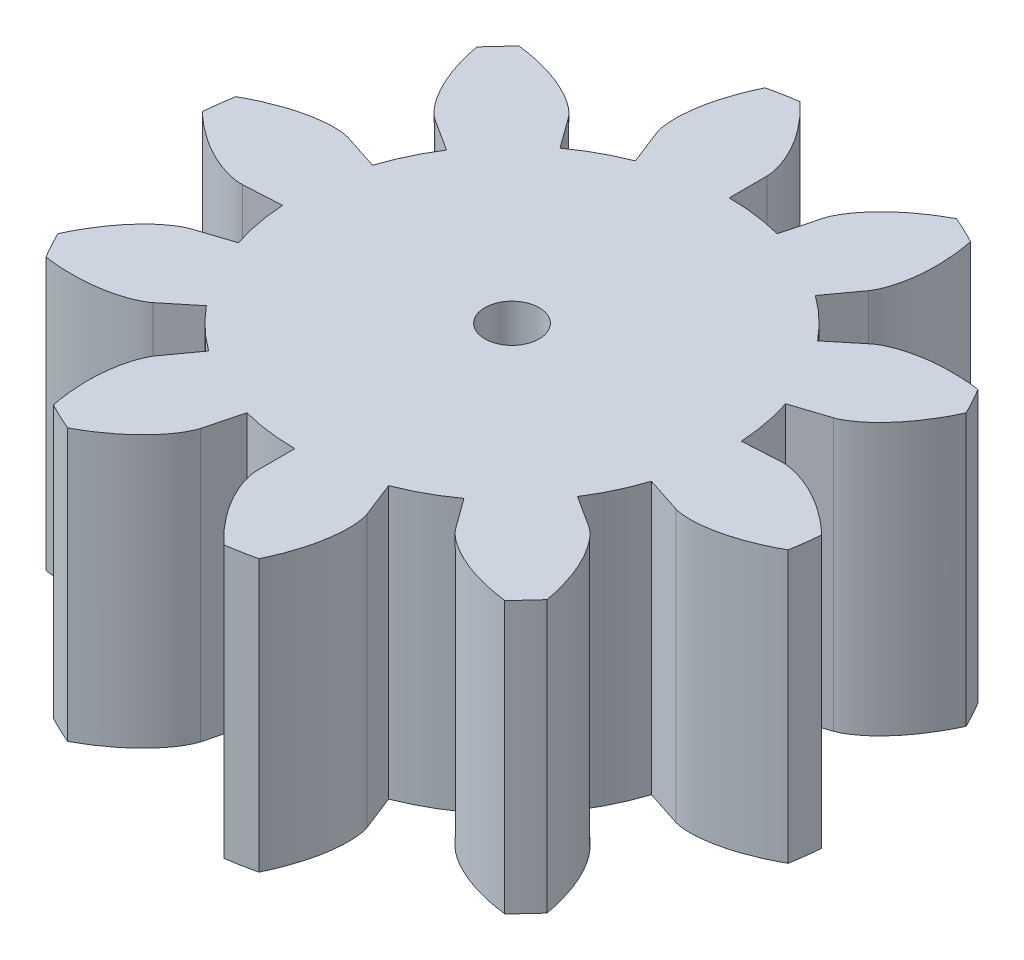
SolidWorks part; units mm, degrees
ref_plane "Front Plane" through (0, 0, 0) normal (0, 0, 1) x (1, 0, 0)
ref_plane "Top Plane" through (0, 0, 0) normal (0, 1, 0) x (1, 0, 0)
ref_plane "Right Plane" through (0, 0, 0) normal (1, 0, 0) x (0, 0, -1)
sketch "Reference attributes" plane through (0, 0, 0) normal (0, 1, 0) x (1, 0, 0)
  line L0 (0, 0) -> (10, 0) construction
  line L1 (0, -10) -> (2, -10) construction
  line L2 (0, 0) -> (9.6593, 2.5882) construction
  line L3 (0, 0) -> (9.3969, 3.4202) construction
  dimension "Teeth" = 10
  dimension "Module" = 2
  dimension "D2" = 10
  dimension "Helix Angle" = 15
  dimension "Pressure angle" = 20
sketch "Gear billet" plane through (0, 0, 0) normal (0, 1, 0) x (1, 0, 0)
  circle A0 centre (0, 0) radius 12.5
  dimension "OuterDi" = 25
extrude "Gear billet Extrude" add sketch "Gear billet" along normal blind 10
ref_plane "Opposite gear face" through (0, 10, 0) normal (0, 1, 0) x (1, 0, 0)
ref_point "Twist centre point top"
ref_point "Twist centre point bottom"
ref_axis "Axis" through (0, 10, 0) along (0, -1, 0)
sketch "Involute Profile" plane through (0, 10, 0) normal (0, 1, 0) x (1, 0, 0)
  line L0 (0, 0) -> (0, 9.3969) construction
  line L1 (0, 0) -> (2.3827, 9.0898) construction
  circle A0 centre (0, 0) radius 10.5
  circle A4 centre (0, 0) radius 9.3969 construction
  spline S0 degree 4 poles (0, 9.3969) (0, 9.4259) (-0.0038, 9.5071) (-0.0266, 9.6606) (-0.0851, 9.9058) (-0.1922, 10.2147) (-0.3651, 10.5975) (-0.6097, 11.0246) (-0.9202, 11.4673) (-1.2957, 11.9131) (-1.705, 12.3279) (-2.1431, 12.7121) (-2.6286, 13.0837) (-3.259, 13.5029) (-4.0497, 13.94) (-5.0111, 14.3602) (-6.121, 14.7192) (-7.2579, 14.9752) (-8.4139, 15.1318) (-9.5763, 15.1949) (-10.744, 15.1661) (-11.8996, 15.0541) (-13.0558, 14.8555) (-14.0345, 14.6214) (-14.8913, 14.3621) (-15.4972, 14.1535) (-16.03, 13.95) (-16.3797, 13.8071) (-16.869, 13.5964) (-17.2328, 13.4235) (-17.5961, 13.248) (-17.7759, 13.1522) (-17.8926, 13.0925) knots 0 0 0 0 0 0.005604 0.015718 0.02996 0.048734 0.068727 0.096889 0.125051 0.153212 0.181374 0.209535 0.237696 0.271429 0.327752 0.384075 0.440398 0.496721 0.553044 0.609367 0.66569 0.722013 0.778336 0.834659 0.86282 0.890982 0.909091 0.931818 0.954545 0.977273 1 1 1 1 1 construction
  spline S1 degree 4 poles (0, 9.3969) (0, 9.4259) (-0.0038, 9.5071) (-0.0266, 9.6606) (-0.0851, 9.9058) (-0.1922, 10.2147) (-0.3651, 10.5975) (-0.6097, 11.0246) (-0.9202, 11.4673) (-1.2957, 11.9131) (-1.705, 12.3279) (-2.1431, 12.7121) (-2.6286, 13.0837) (-3.259, 13.5029) (-4.0497, 13.94) (-5.0111, 14.3602) (-6.121, 14.7192) (-7.2579, 14.9752) (-8.4139, 15.1318) (-9.5763, 15.1949) (-10.744, 15.1661) (-11.8996, 15.0541) (-13.0558, 14.8555) (-14.0345, 14.6214) (-14.8913, 14.3621) (-15.4972, 14.1535) (-15.9054, 13.9976) (-16.1073, 13.9173) (-16.1861, 13.8853) knots 0 0 0 0 0 0.005604 0.015718 0.02996 0.048734 0.068727 0.096889 0.125051 0.153212 0.181374 0.209535 0.237696 0.271429 0.327752 0.384075 0.440398 0.496721 0.553044 0.609367 0.66569 0.722013 0.778336 0.834659 0.86282 0.890982 0.909091 0.909091 0.909091 0.909091 0.909091
  spline S2 degree 4 poles (2.3827, 9.0898) (2.3901, 9.1179) (2.4144, 9.1954) (2.4753, 9.3382) (2.5941, 9.5605) (2.776, 9.8321) (3.0403, 10.1585) (3.3853, 10.5097) (3.7979, 10.8592) (4.2741, 11.1952) (4.7752, 11.4927) (5.2964, 11.7532) (5.8603, 11.9896) (6.5764, 12.2353) (7.452, 12.4575) (8.4886, 12.6202) (9.6532, 12.6861) (10.8179, 12.6455) (11.9759, 12.5038) (13.1163, 12.27) (14.2385, 11.9461) (15.3279, 11.5447) (16.3959, 11.0595) (17.2833, 10.5849) (18.0464, 10.1168) (18.5796, 9.7614) (19.0434, 9.4294) (19.3453, 9.2025) (19.7652, 8.8746) (20.0733, 8.6152) (20.3803, 8.3532) (20.5299, 8.215) (20.6277, 8.1276) knots 0 0 0 0 0 0.005604 0.015718 0.02996 0.048734 0.068727 0.096889 0.125051 0.153212 0.181374 0.209535 0.237696 0.271429 0.327752 0.384075 0.440398 0.496721 0.553044 0.609367 0.66569 0.722013 0.778336 0.834659 0.86282 0.890982 0.909091 0.931818 0.954545 0.977273 1 1 1 1 1 construction
  spline S3 degree 4 poles (2.3827, 9.0898) (2.3901, 9.1179) (2.4144, 9.1954) (2.4753, 9.3382) (2.5941, 9.5605) (2.776, 9.8321) (3.0403, 10.1585) (3.3853, 10.5097) (3.7979, 10.8592) (4.2741, 11.1952) (4.7752, 11.4927) (5.2964, 11.7532) (5.8603, 11.9896) (6.5764, 12.2353) (7.452, 12.4575) (8.4886, 12.6202) (9.6532, 12.6861) (10.8179, 12.6455) (11.9759, 12.5038) (13.1163, 12.27) (14.2385, 11.9461) (15.3279, 11.5447) (16.3959, 11.0595) (17.2833, 10.5849) (18.0464, 10.1168) (18.5796, 9.7614) (18.9349, 9.5071) (19.1098, 9.3782) (19.1779, 9.3273) knots 0 0 0 0 0 0.005604 0.015718 0.02996 0.048734 0.068727 0.096889 0.125051 0.153212 0.181374 0.209535 0.237696 0.271429 0.327752 0.384075 0.440398 0.496721 0.553044 0.609367 0.66569 0.722013 0.778336 0.834659 0.86282 0.890982 0.909091 0.909091 0.909091 0.909091 0.909091
  point P6 (-0.324, 10.495)
  point P11 (2.9746, 10.0698)
  dimension "BaseDi" = 18.7939
  dimension "Adjusted Reference Diameter" = 21
  dimension "Reference Circumferential pitch" = 3.2987
sketch "Tooth profile" plane through (0, 10, 0) normal (0, 1, 0) x (1, 0, 0)
  line L0 (0, 0) -> (0, 9.3969) construction
  line L1 (0, 0) -> (2.3827, 9.0898) construction
  line L2 (0, 0) -> (0, 9.3969)
  line L3 (0, 0) -> (2.3827, 9.0898)
  line L4 (-0.2, -1.5517) -> (-0.2, 9.3969) construction
  line L5 (-0.2, -1.5517) -> (2.5762, 9.0391) construction
  circle A0 centre (0, 0) radius 12.5 construction
  circle A1 centre (0, 0) radius 12.5
  circle A2 centre (0, 0) radius 8
  spline S0 degree 1 poles (-0.2, 9.3969) (-16.1108, 13.7) knots 0 0 1 1 construction
  spline S1 degree 4 poles (-1998.2492, 88.8187) (-50.4033, 5.2802) (-1.0936, 5.8123) (0.3671, 8.0116) (-0.0851, 9.9058) (-0.1922, 10.2147) (-0.3651, 10.5975) (-0.6097, 11.0246) (-0.9202, 11.4673) (-1.2957, 11.9131) (-1.705, 12.3279) (-2.1431, 12.7121) (-2.6286, 13.0837) (-3.259, 13.5029) (-4.0497, 13.94) (-5.0111, 14.3602) (-6.121, 14.7192) (-7.2579, 14.9752) (-8.4139, 15.1318) (-9.5763, 15.1949) (-10.744, 15.1661) (-11.8996, 15.0541) (-13.0558, 14.8555) (-14.0345, 14.6214) (-14.8913, 14.3621) (-17.0967, 13.603) (-21.053, 11.7501) (19.7443, 27.8049) (-1868.6592, -739.8621) knots -0.32772 -0.32772 -0.32772 -0.32772 -0.32772 0.005604 0.015718 0.02996 0.048734 0.068727 0.096889 0.125051 0.153212 0.181374 0.209535 0.237696 0.271429 0.327752 0.384075 0.440398 0.496721 0.553044 0.609367 0.66569 0.722013 0.778336 0.834659 0.86282 0.890982 1.254286 1.254286 1.254286 1.254286 1.254286 only from (0, 9.3969) to (-16.1861, 13.8853) construction
  spline S2 degree 4 poles (1955.4641, -420.7716) (50.0949, -7.6729) (2.5317, 5.3451) (1.6763, 7.8429) (2.5941, 9.5605) (2.776, 9.8321) (3.0403, 10.1585) (3.3853, 10.5097) (3.7979, 10.8592) (4.2741, 11.1952) (4.7752, 11.4927) (5.2964, 11.7532) (5.8603, 11.9896) (6.5764, 12.2353) (7.452, 12.4575) (8.4886, 12.6202) (9.6532, 12.6861) (10.8179, 12.6455) (11.9759, 12.5038) (13.1163, 12.27) (14.2385, 11.9461) (15.3279, 11.5447) (16.3959, 11.0595) (17.2833, 10.5849) (18.0464, 10.1168) (19.9872, 8.8233) (23.3444, 6.0278) (-12.0487, 31.9027) (1619.9843, -1189.51) knots -0.32772 -0.32772 -0.32772 -0.32772 -0.32772 0.005604 0.015718 0.02996 0.048734 0.068727 0.096889 0.125051 0.153212 0.181374 0.209535 0.237696 0.271429 0.327752 0.384075 0.440398 0.496721 0.553044 0.609367 0.66569 0.722013 0.778336 0.834659 0.86282 0.890982 1.254286 1.254286 1.254286 1.254286 1.254286 only from (2.3827, 9.0898) to (19.1779, 9.3273) construction
  spline S3 degree 1 poles (2.5762, 9.0391) (19.0581, 9.1671) knots 0 0 1 1 construction
  spline S4 degree 4 poles (0, 9.3969) (0, 9.4259) (-0.0038, 9.5071) (-0.0266, 9.6606) (-0.0851, 9.9058) (-0.1922, 10.2147) (-0.3651, 10.5975) (-0.6097, 11.0246) (-0.9202, 11.4673) (-1.2957, 11.9131) (-1.705, 12.3279) (-2.1431, 12.7121) (-2.6286, 13.0837) (-3.259, 13.5029) (-4.0497, 13.94) (-5.0111, 14.3602) (-6.121, 14.7192) (-7.2579, 14.9752) (-8.4139, 15.1318) (-9.5763, 15.1949) (-10.744, 15.1661) (-11.8996, 15.0541) (-13.0558, 14.8555) (-14.0345, 14.6214) (-14.8913, 14.3621) (-15.4972, 14.1535) (-15.9054, 13.9976) (-16.1073, 13.9173) (-16.1861, 13.8853) knots 0 0 0 0 0 0.005604 0.015718 0.02996 0.048734 0.068727 0.096889 0.125051 0.153212 0.181374 0.209535 0.237696 0.271429 0.327752 0.384075 0.440398 0.496721 0.553044 0.609367 0.66569 0.722013 0.778336 0.834659 0.86282 0.890982 0.909091 0.909091 0.909091 0.909091 0.909091
  spline S5 degree 4 poles (2.3827, 9.0898) (2.3901, 9.1179) (2.4144, 9.1954) (2.4753, 9.3382) (2.5941, 9.5605) (2.776, 9.8321) (3.0403, 10.1585) (3.3853, 10.5097) (3.7979, 10.8592) (4.2741, 11.1952) (4.7752, 11.4927) (5.2964, 11.7532) (5.8603, 11.9896) (6.5764, 12.2353) (7.452, 12.4575) (8.4886, 12.6202) (9.6532, 12.6861) (10.8179, 12.6455) (11.9759, 12.5038) (13.1163, 12.27) (14.2385, 11.9461) (15.3279, 11.5447) (16.3959, 11.0595) (17.2833, 10.5849) (18.0464, 10.1168) (18.5796, 9.7614) (18.9349, 9.5071) (19.1098, 9.3782) (19.1779, 9.3273) knots 0 0 0 0 0 0.005604 0.015718 0.02996 0.048734 0.068727 0.096889 0.125051 0.153212 0.181374 0.209535 0.237696 0.271429 0.327752 0.384075 0.440398 0.496721 0.553044 0.609367 0.66569 0.722013 0.778336 0.834659 0.86282 0.890982 0.909091 0.909091 0.909091 0.909091 0.909091
  spline S6 degree 3 poles (-16.1108, 13.7) (-16.026, 13.7345) (-15.864, 13.7986) (-15.4713, 13.9483) (-14.8419, 14.1693) (-13.5365, 14.5594) (-11.6365, 14.9237) (-9.3123, 15.0305) (-7.0032, 14.7707) (-4.7771, 14.1111) (-3.0723, 13.1997) (-1.8755, 12.2396) (-1.094, 11.3996) (-0.5731, 10.6072) (-0.2891, 9.9066) (-0.2, 9.5714) (-0.2, 9.3969) knots 0 0 0 0 0.014205 0.028409 0.056818 0.113636 0.227273 0.340909 0.454545 0.568182 0.681818 0.738636 0.795455 0.852273 0.880682 0.909091 0.909091 0.909091 0.909091 construction
  spline S7 degree 3 poles (2.5762, 9.0391) (2.6205, 9.2079) (2.7916, 9.5095) (3.244, 10.1153) (3.9487, 10.7496) (4.9177, 11.364) (6.3188, 11.9892) (8.1991, 12.4386) (10.5196, 12.5122) (12.8192, 12.178) (15.0403, 11.4854) (16.7859, 10.6512) (17.9497, 9.9428) (18.5024, 9.5694) (18.8444, 9.3251) (18.9848, 9.222) (19.0581, 9.1671) knots 0 0 0 0 0.028409 0.056818 0.113636 0.170455 0.227273 0.340909 0.454545 0.568182 0.681818 0.795455 0.852273 0.880682 0.894886 0.909091 0.909091 0.909091 0.909091 construction
  dimension "RootDi" = 16
  dimension "Offset" = 0.2
extrude "Cut tooth profile" cut sketch "Tooth profile" against normal up to next contours A1 region at (1.3635, 10, -10.5787)
sketch "Tooth profile OFFSET" plane through (0, 10, 0) normal (0, 1, 0) x (1, 0, 0)
  line L4 (-0.1, -0.7759) -> (-0.1, 9.3969)
  line L5 (2.4795, 9.0645) -> (-0.1, -0.7759)
  line L6 (-0.1, -0.7759) -> (-0.1, 9.3969)
  line L7 (2.4795, 9.0645) -> (-0.1, -0.7759)
  circle A3 centre (0, 0) radius 12.5 construction
  circle A4 centre (0, 0) radius 12.5
  circle A6 centre (0, 0) radius 7.9
  circle A7 centre (0, 0) radius 7.9
  spline S4 degree 3 poles (2415.4578, -1795.2758) (-11.1045, 26.032) (25.2251, 4.8292) (18.8161, 9.4682) (18.7315, 9.5287) (18.5637, 9.6465) (18.4806, 9.7038) (18.3187, 9.8134) (18.2393, 9.866) (17.8397, 10.1264) (17.5022, 10.3322) (16.8218, 10.7159) (16.4788, 10.8937) (15.7764, 11.2285) (15.418, 11.3848) (14.3314, 11.8116) (13.5867, 12.0436) (12.0698, 12.388) (11.2977, 12.5003) (9.7459, 12.5878) (8.9659, 12.5631) (7.4271, 12.3571) (6.6678, 12.1758) (5.2165, 11.6331) (4.5224, 11.2719) (3.6019, 10.5711) (3.3151, 10.3109) (2.9393, 9.8761) (2.8228, 9.7236) (2.6701, 9.4834) (2.6229, 9.4014) (-0.0522, 4.0526) (14.774, -7.7312) (2833.3221, 1001.4016) knots -1.232193 -1.232193 -1.232193 -1.232193 0.015625 0.015625 0.03125 0.03125 0.046875 0.046875 0.0625 0.0625 0.125 0.125 0.1875 0.1875 0.25 0.25 0.375 0.375 0.5 0.5 0.625 0.625 0.75 0.75 0.875 0.875 0.9375 0.9375 0.96875 0.96875 0.984375 0.984375 1.963375 1.963375 1.963375 1.963375 only from (19.118, 9.2472) to (2.4795, 9.0645)
  spline S5 degree 3 poles (-2486.7613, 1687.0789) (-16.2513, -3.7322) (1.0781, 3.9069) (-0.1533, 9.7592) (-0.1781, 9.8505) (-0.265, 10.1216) (-0.339, 10.2986) (-0.5923, 10.8145) (-0.8037, 11.1389) (-1.5164, 12.0503) (-2.0962, 12.5756) (-3.3625, 13.4686) (-4.0511, 13.8365) (-5.4873, 14.426) (-6.2355, 14.6476) (-7.7588, 14.9564) (-8.5342, 15.0436) (-10.0888, 15.0951) (-10.8681, 15.0595) (-12.0273, 14.9222) (-12.4136, 14.8619) (-13.178, 14.7161) (-13.5548, 14.6311) (-14.3103, 14.4325) (-14.689, 14.319) (-15.1416, 14.1685) (-15.2316, 14.1377) (-15.4161, 14.0727) (-15.5109, 14.0384) (-15.7032, 13.9669) (-15.8004, 13.9299) (-23.1763, 11.0676) (17.3433, 22.3658) (-2791.8274, -1124.1627) knots -0.96337 -0.96337 -0.96337 -0.96337 0.015625 0.015625 0.03125 0.03125 0.0625 0.0625 0.125 0.125 0.25 0.25 0.375 0.375 0.5 0.5 0.625 0.625 0.75 0.75 0.8125 0.8125 0.875 0.875 0.9375 0.9375 0.953125 0.953125 0.96875 0.96875 0.984375 0.984375 2.232207 2.232207 2.232207 2.232207 only from (-0.1, 9.3969) to (-16.1485, 13.7926)
  spline S6 degree 3 poles (19.118, 9.2472) (19.0472, 9.3001) (18.9747, 9.3535) (18.8161, 9.4682) (18.7315, 9.5287) (18.5637, 9.6465) (18.4806, 9.7038) (18.3187, 9.8134) (18.2393, 9.866) (17.8397, 10.1264) (17.5022, 10.3322) (16.8218, 10.7159) (16.4788, 10.8937) (15.7764, 11.2285) (15.418, 11.3848) (14.3314, 11.8116) (13.5867, 12.0436) (12.0698, 12.388) (11.2977, 12.5003) (9.7459, 12.5878) (8.9659, 12.5631) (7.4271, 12.3571) (6.6678, 12.1758) (5.2165, 11.6331) (4.5224, 11.2719) (3.6019, 10.5711) (3.3151, 10.3109) (2.9393, 9.8761) (2.8228, 9.7236) (2.6701, 9.4834) (2.6229, 9.4014) (2.5388, 9.2333) (2.5013, 9.1476) (2.4795, 9.0645) knots 0 0 0 0 0.015625 0.015625 0.03125 0.03125 0.046875 0.046875 0.0625 0.0625 0.125 0.125 0.1875 0.1875 0.25 0.25 0.375 0.375 0.5 0.5 0.625 0.625 0.75 0.75 0.875 0.875 0.9375 0.9375 0.96875 0.96875 0.984375 0.984375 1 1 1 1
  spline S7 degree 3 poles (-0.1, 9.3969) (-0.1, 9.4829) (-0.1146, 9.5753) (-0.1533, 9.7592) (-0.1781, 9.8505) (-0.265, 10.1216) (-0.339, 10.2986) (-0.5923, 10.8145) (-0.8037, 11.1389) (-1.5164, 12.0503) (-2.0962, 12.5756) (-3.3625, 13.4686) (-4.0511, 13.8365) (-5.4873, 14.426) (-6.2355, 14.6476) (-7.7588, 14.9564) (-8.5342, 15.0436) (-10.0888, 15.0951) (-10.8681, 15.0595) (-12.0273, 14.9222) (-12.4136, 14.8619) (-13.178, 14.7161) (-13.5548, 14.6311) (-14.3103, 14.4325) (-14.689, 14.319) (-15.1416, 14.1685) (-15.2316, 14.1377) (-15.4161, 14.0727) (-15.5109, 14.0384) (-15.7032, 13.9669) (-15.8004, 13.9299) (-15.9828, 13.8591) (-16.0665, 13.8259) (-16.1485, 13.7926) knots 0 0 0 0 0.015625 0.015625 0.03125 0.03125 0.0625 0.0625 0.125 0.125 0.25 0.25 0.375 0.375 0.5 0.5 0.625 0.625 0.75 0.75 0.8125 0.8125 0.875 0.875 0.9375 0.9375 0.953125 0.953125 0.96875 0.96875 0.984375 0.984375 1 1 1 1
  line M3 (0, 8) -> (0, 9.3969)
  spline M4 degree 4 poles (0, 9.3969) (0, 9.4259) (-0.0038, 9.5071) (-0.0266, 9.6606) (-0.0851, 9.9058) (-0.1922, 10.2147) (-0.3651, 10.5975) (-0.6097, 11.0246) (-0.9202, 11.4673) (-1.2957, 11.9131) (-1.705, 12.3279) (-2.1431, 12.7121) (-2.6286, 13.0837) (-3.259, 13.5029) (-4.0497, 13.94) (-5.0111, 14.3602) (-6.121, 14.7192) (-7.2579, 14.9752) (-8.4139, 15.1318) (-9.5763, 15.1949) (-10.744, 15.1661) (-11.8996, 15.0541) (-13.0558, 14.8555) (-14.0345, 14.6214) (-14.8913, 14.3621) (-15.4972, 14.1535) (-15.9054, 13.9976) (-16.1073, 13.9173) (-16.1861, 13.8853) knots 0 0 0 0 0 0.005604 0.015718 0.02996 0.048734 0.068727 0.096889 0.125051 0.153212 0.181374 0.209535 0.237696 0.271429 0.327752 0.384075 0.440398 0.496721 0.553044 0.609367 0.66569 0.722013 0.778336 0.834659 0.86282 0.890982 0.909091 0.909091 0.909091 0.909091 0.909091 only from (0, 9.3969) to (-1.7676, 12.3744)
  arc M5 (-1.7676, 12.3744) -> (4.8476, 11.5218) centre (0, 0) ccw
  spline M6 degree 4 poles (19.1779, 9.3273) (19.1098, 9.3782) (18.9349, 9.5071) (18.5796, 9.7614) (18.0464, 10.1168) (17.2833, 10.5849) (16.3959, 11.0595) (15.3279, 11.5447) (14.2385, 11.9461) (13.1163, 12.27) (11.9759, 12.5038) (10.8179, 12.6455) (9.6532, 12.6861) (8.4886, 12.6202) (7.452, 12.4575) (6.5764, 12.2353) (5.8603, 11.9896) (5.2964, 11.7532) (4.7752, 11.4927) (4.2741, 11.1952) (3.7979, 10.8592) (3.3853, 10.5097) (3.0403, 10.1585) (2.776, 9.8321) (2.5941, 9.5605) (2.4753, 9.3382) (2.4144, 9.1954) (2.3901, 9.1179) (2.3827, 9.0898) knots 0 0 0 0 0 0.018109 0.04627 0.074432 0.130755 0.187078 0.243401 0.299724 0.356047 0.41237 0.468693 0.525016 0.581339 0.637662 0.671395 0.699556 0.727717 0.755879 0.78404 0.812202 0.840364 0.860357 0.879131 0.893373 0.903487 0.909091 0.909091 0.909091 0.909091 0.909091 only from (4.8476, 11.5218) to (2.3827, 9.0898)
  line M7 (2.3827, 9.0898) -> (2.0285, 7.7385)
  arc M8 (2.0285, 7.7385) -> (0, 8) centre (0, 0) ccw
  dimension "Offset" = 0.1
  dimension "D2" = 0.1
extrude "Cut Tooth profile OFFSET" [suppressed] cut sketch "Tooth profile OFFSET" against normal up to surface (10 mm away) contours S7 L6 A7 L7 S6 A4 M6 M7 M8 M3 M4 M5
sketch "Tangent meshing reference" plane through (0, 10, 0) normal (0, 1, 0) x (1, 0, 0)
  circle A0 centre (0, 0) radius 10.5 construction
  circle A1 centre (0, 0) radius 10.5
sketch "Gear ratio reference" plane through (0, 10, 0) normal (0, 1, 0) x (1, 0, 0)
  circle A0 centre (0, 0) radius 10
  dimension "Reference diameter" = 20
pattern_circular "Duplicate teeth" count 10 over 360 about axis through (0, 10, 0) along (0, -1, 0) of "Cut tooth profile"
other "Twist Left" [suppressed] parameters "D0"=14.621
other "Twist Right" [suppressed] parameters "D0"=14.621
mirror "Herringbone Mirror" [suppressed] about plane through (0, 10, 0) normal (0, 1, 0) of bodies 259
sketch "Sketch1" plane through (0, 0, 0) normal (0, -1, 0) x (1, 0, 0)
  circle A0 centre (0, 0) radius 1
  dimension "D1" = 2
extrude "Cut-Extrude1" cut sketch "Sketch1" against normal up to surface (10 mm away) up to face at (0, 10, 0)
equation "\"D1@Duplicate teeth\"=\"Teeth@Reference attributes\""
equation "\"twist\"= \"suppressed\""
equation "\"D2@Tooth profile OFFSET\"=\"Offset@Tooth profile OFFSET\""
